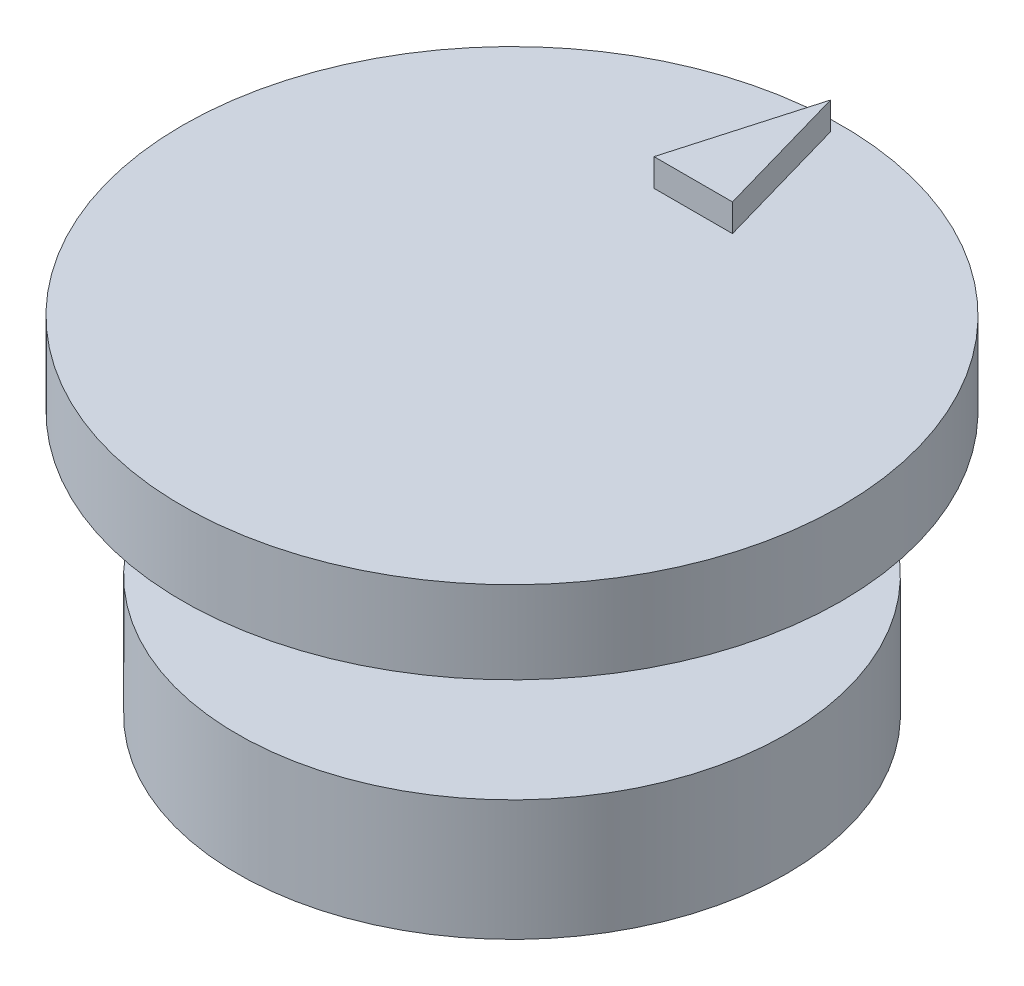
SolidWorks part; units mm, degrees
ref_plane "Front Plane" through (0, 0, 0) normal (0, 0, 1) x (1, 0, 0)
ref_plane "Top Plane" through (0, 0, 0) normal (0, 1, 0) x (1, 0, 0)
ref_plane "Right Plane" through (0, 0, 0) normal (1, 0, 0) x (0, 0, -1)
sketch "Sketch1" plane through (0, 0, 0) normal (0, 0, 1) x (1, 0, 0)
  line L0 (0, -20.8911) -> (0, -36.8931)
  line L1 (0, -36.8931) -> (12.7, -36.8931)
  line L2 (12.7, -36.8931) -> (12.7, -31.3051)
  line L3 (12.7, -31.3051) -> (3.175, -31.3051)
  line L4 (3.175, -31.3051) -> (3.175, -26.2251)
  line L5 (3.175, -26.2251) -> (12.7, -26.2251)
  line L6 (12.7, -26.2251) -> (12.7, -24.7011)
  line L7 (12.7, -24.7011) -> (15.24, -24.7011)
  line L8 (15.24, -24.7011) -> (15.24, -20.8911)
  line L9 (15.24, -20.8911) -> (0, -20.8911)
  dimension "D1" = 3.175
  dimension "D2" = 9.525
  dimension "D3" = 5.08
  dimension "D4" = 5.588
  dimension "D5" = 1.524
  dimension "D6" = 3.81
  dimension "D7" = 12.7
  dimension "D8" = 15.24
revolve "dial base shape" add sketch "Sketch1" angle 360 about L0
sketch "Sketch2" plane through (0, -20.8911, 0) normal (0, 1, 0) x (1, 0, 0)
  line L0 (0, 14.732) -> (-1.8139, 8.382)
  line L1 (-1.8139, 8.382) -> (1.8139, 8.382)
  line L2 (1.8139, 8.382) -> (0, 14.732)
  dimension "D1" = 6.35
  dimension "D2" = 8.382
  dimension "D3" = 6.604
  dimension "D4" = 6.604
extrude "arrow" add sketch "Sketch2" along normal blind 1.27
sketch "Sketch3" plane through (0, -36.8931, 0) normal (0, -1, 0) x (1, 0, 0)
  circle A0 centre (0, -9.8549) radius 2.286
  dimension "D1" = 4.572
extrude "flag" add sketch "Sketch3" along normal blind 2.54
fillet "round out the bottom" radius 1.27 1 edges at (-2.286, -36.8931, -9.8549)
